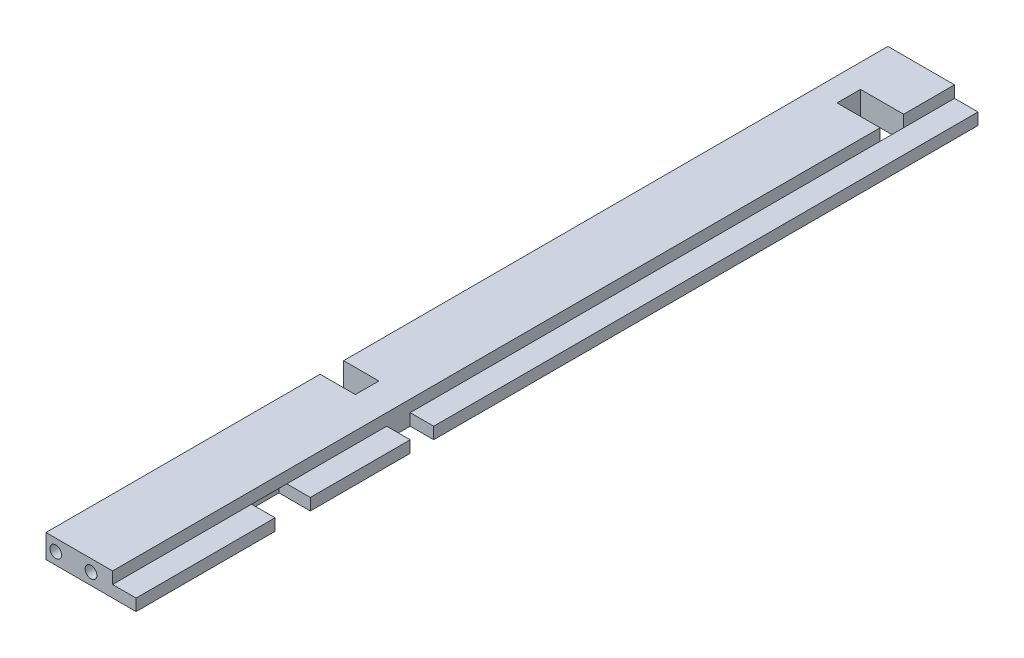
SolidWorks part; units mm, degrees
material "Plywood"
ref_plane "Plan de face" through (0, 0, 0) normal (0, 0, 1) x (1, 0, 0)
ref_plane "Plan de dessus" through (0, 0, 0) normal (0, 1, 0) x (1, 0, 0)
ref_plane "Plan de droite" through (0, 0, 0) normal (1, 0, 0) x (0, 0, -1)
sketch "Esquisse1" plane through (0, 0, 0) normal (0, 0, 1) x (1, 0, 0)
  line L0 (0, 0) -> (0, 6)
  line L1 (0, 6) -> (17, 6)
  line L2 (17, 6) -> (17, 3)
  line L3 (17, 3) -> (23, 3)
  line L4 (23, 3) -> (23, 0)
  line L5 (23, 0) -> (0, 0)
  dimension "D1" = 6
  dimension "D2" = 3
  dimension "D3" = 6
  dimension "D4" = 23
extrude "Boss.-Extru.1" add sketch "Esquisse1" along normal blind 215
sketch "Esquisse3" plane through (0, 0, 0) normal (0, -1, 0) x (1, 0, 0)
  line L0 (23, 215) -> (23, 0) construction
  line L1 (23, 170.5) -> (15, 170.5)
  line L2 (23, 170.5) -> (23, 179.5)
  line L3 (23, 179.5) -> (15, 179.5)
  line L4 (15, 170.5) -> (15, 179.5)
  line L5 (0, 215) -> (0, 0) construction
  line L6 (0, 170.5) -> (9, 170.5)
  line L7 (0, 170.5) -> (0, 179.5)
  line L8 (0, 179.5) -> (9, 179.5)
  line L9 (9, 170.5) -> (9, 179.5)
  line L10 (-2, 179.5) -> (9, 179.5) construction
  line L11 (-2, 170.5) -> (9, 170.5) construction
  line L12 (9, 179.5) -> (9, 170.5) construction
  line L13 (15, 179.5) -> (15, 170.5) construction
extrude "Enlèv. mat.-Extru.1" cut sketch "Esquisse3" against normal blind 3
sketch "Esquisse4" plane through (0, 0, 0) normal (0, -1, 0) x (1, 0, 0)
  line L0 (0, 170.5) -> (0, 0) construction
  line L1 (0, 139) -> (9, 139)
  line L2 (0, 139) -> (0, 145)
  line L3 (0, 145) -> (9, 145)
  line L4 (9, 139) -> (9, 145)
  line L5 (-1, 139) -> (9, 139) construction
  line L6 (-1, 145) -> (9, 145) construction
  line L7 (9, 145) -> (9, 139) construction
extrude "Enlèv. mat.-Extru.2" cut sketch "Esquisse4" against normal through all
sketch "Esquisse5" plane through (0, 0, 0) normal (0, -1, 0) x (1, 0, 0)
  line L0 (23, 170.5) -> (23, 0) construction
  line L1 (23, 139) -> (17, 139)
  line L2 (23, 139) -> (23, 145)
  line L3 (23, 145) -> (17, 145)
  line L4 (17, 139) -> (17, 145)
  line L5 (23, 139) -> (17, 139) construction
  line L6 (17, 145) -> (23, 145) construction
  line L7 (17, 145) -> (17, 139) construction
extrude "Enlèv. mat.-Extru.3" cut sketch "Esquisse5" against normal blind 3
sketch "Esquisse8" plane through (0, 0, 215) normal (0, 0, 1) x (1, 0, 0)
  line L0 (0, 0) -> (23, 0) construction
  line L1 (0, 6) -> (0, 0) construction
  circle A0 centre (2.5, 3) radius 1.5
  dimension "D1" = 3
  dimension "D2" = 3
  dimension "D3" = 2.5
extrude "Enlèv. mat.-Extru.4" cut sketch "Esquisse8" against normal blind 10
pattern_linear "Répétition linéaire1" count 2 spacing 9 along (1, 0, 0) of "Enlèv. mat.-Extru.4"
sketch "Esquisse9" plane through (0, 6, 0) normal (0, 1, 0) x (1, 0, 0)
  line L0 (17, -215) -> (17, 0) construction
  line L1 (6, -19) -> (17, -19)
  line L2 (6, -19) -> (6, -13)
  line L3 (6, -13) -> (17, -13)
  line L4 (17, -19) -> (17, -13)
  line L5 (6, -19) -> (6, -13) construction
  line L6 (6, -13) -> (17, -13) construction
  line L7 (6, -19) -> (17, -19) construction
  dimension "D1" = 0
  dimension "D2" = 0
  dimension "D3" = 0
extrude "Enlèv. mat.-Extru.5" cut sketch "Esquisse9" against normal through all
